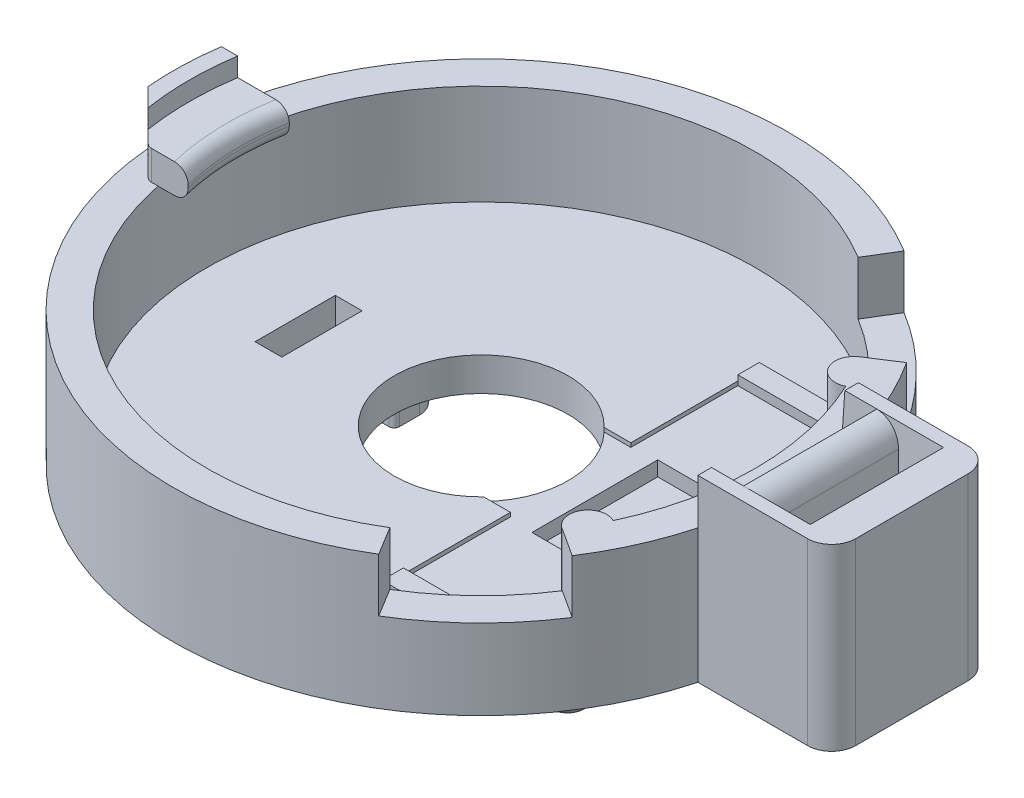
SolidWorks part; units mm, degrees
ref_plane "Спереди" through (0, 0, 0) normal (0, 0, 1) x (1, 0, 0)
ref_plane "Сверху" through (0, 0, 0) normal (0, 1, 0) x (1, 0, 0)
ref_plane "Справа" through (0, 0, 0) normal (1, 0, 0) x (0, 0, -1)
sketch "Sketch3" plane through (0, 0, 0) normal (0, 1, 0) x (1, 0, 0)
  circle A0 centre (0, 0) radius 11.5
  dimension "D1" = 23
extrude "Boss-Extrude2" add sketch "Sketch3" along normal blind 5
sketch "Sketch4" plane through (0, 5, 0) normal (0, 1, 0) x (1, 0, 0)
  circle A0 centre (0, 0) radius 10.25
  dimension "D1" = 20.5
extrude "Cut-Extrude2" cut sketch "Sketch4" against normal offset from surface (3.75 mm away) 1.25 up to face at (0, 0, 11.5)
sketch "Sketch5" plane through (0, 0, 0) normal (0, -1, 0) x (1, 0, 0)
  line L0 (11.1018, 0) -> (0, 0) construction
  line L1 (11.1018, 3) -> (16.1, 3)
  line L2 (11.1018, 3) -> (11.1018, -3)
  line L3 (11.1018, -3) -> (16.1, -3)
  line L4 (16.1, 3) -> (16.1, -3)
  line L5 (-11.5, 0) -> (0, 0) construction
  circle A0 centre (0, 0) radius 11.5 construction
  dimension "D1" = 6
  dimension "D2" = 27.6
extrude "Boss-Extrude3" add sketch "Sketch5" against normal blind 6.7
fillet "Fillet1" radius 0.9 2 edges at (16.1, 3.35, -3) (16.1, 3.35, 3)
sketch "Sketch6" plane through (0, 1.25, 0) normal (0, 1, 0) x (1, 0, 0)
  circle A0 centre (0, 0) radius 3.25
  dimension "D1" = 6.5
extrude "Cut-Extrude3" cut sketch "Sketch6" against normal through all
sketch "Sketch8" plane through (0, 5, 0) normal (0, 1, 0) x (1, 0, 0)
  line L0 (5.9896, 9.8171) -> (5.3385, 8.75)
  line L1 (9.6534, 6.25) -> (8.6041, 5.5707)
  line L2 (9.6534, -6.25) -> (8.6041, -5.5707)
  line L3 (5.9896, -9.8171) -> (5.3385, -8.75)
  line L4 (5.3385, 8.75) -> (0, 0) construction
  line L5 (0, 0) -> (8.6041, 5.5707) construction
  line L6 (0, 0) -> (5.3385, -8.75) construction
  line L7 (0, 0) -> (8.6041, -5.5707) construction
  line L8 (9.6534, 6.25) -> (9.6534, -6.25) construction
  line L9 (9.6534, 0) -> (0, 0) construction
  line L10 (5.9896, 9.8171) -> (5.9896, -9.8171) construction
  arc A0 (5.9896, 9.8171) -> (9.6534, 6.25) centre (0, 0) cw
  arc A1 (11.1018, 3) -> (11.1018, -3) centre (0, 0) ccw construction
  arc A2 (9.6534, -6.25) -> (5.9896, -9.8171) centre (0, 0) cw
  arc A3 (5.3385, 8.75) -> (8.6041, 5.5707) centre (-1.1445, -1.1755) cw
  circle A4 centre (0, 0) radius 10.25 construction
  arc A5 (8.6041, -5.5707) -> (5.3385, -8.75) centre (0, 0) cw
  dimension "D1" = 12.5
  dimension "D2" = 17.5
extrude "Cut-Extrude4" cut sketch "Sketch8" against normal blind 2
sketch "Sketch9" plane through (0, 0, 0) normal (0, -1, 0) x (1, 0, 0)
  line L0 (-7.8208, 4.4537) -> (-2.8242, 1.6083) construction
  line L1 (-1.4647, 3.9955) -> (-4.1836, -0.7789) construction
  line L2 (-7.8208, 4.4537) -> (0.0534, -8.9998) construction
  line L3 (0.0534, -8.9998) -> (7.7674, 4.5461) construction
  line L4 (7.7674, 4.5461) -> (-7.8208, 4.4537) construction
  circle A0 centre (7.7674, 4.5461) radius 0.75
  circle A1 centre (0.0534, -8.9998) radius 0.75
  circle A2 centre (-7.8208, 4.4537) radius 0.75
  circle A3 centre (0, 0) radius 9 construction
  circle A5 centre (0, 0) radius 3.25 construction
  dimension "D1" = 1.5
  dimension "D2" = 5.75
  dimension "D3" = 8.25
extrude "Boss-Extrude4" add sketch "Sketch9" along normal blind 1.5
fillet "Fillet2" radius 0.3 3 edges at (7.7674, -1.5, 3.7961) (-7.8208, -1.5, 3.7037) (0.0534, -1.5, -9.7498)
sketch "Sketch10" plane through (0, 0, 0) normal (0, -1, 0) x (1, 0, 0)
  line L0 (0, 0) -> (-11.247, 2.3989) construction
  line L1 (-11.486, -0.5665) -> (-10.2343, -0.5665)
  line L2 (-10.2553, 5.2037) -> (-8.8309, 5.2037)
  arc A0 (-11.486, -0.5665) -> (-10.2553, 5.2037) centre (0, 0) cw
  arc A1 (11.1018, 3) -> (11.1018, -3) centre (0, 0) ccw construction
  arc A2 (-10.2343, -0.5665) -> (-8.8309, 5.2037) centre (0, 0) cw
  arc A3 (5.3385, 8.75) -> (5.3385, -8.75) centre (0, 0) ccw construction
  circle A4 centre (-7.8208, 4.4537) radius 0.75 construction
  dimension "D1" = 5.9
extrude "Boss-Extrude5" add sketch "Sketch10" along normal up to surface (1.5 mm away) up to face at (-7.8208, -1.5, 4.0037)
sketch "Sketch11" plane through (0, 5, 0) normal (0, 1, 0) x (1, 0, 0)
  line L0 (0, 0) -> (-10.9, 0) construction
  line L1 (-11.3777, 1.6727) -> (-10.7709, 1.6727)
  line L2 (-10.7709, -1.6727) -> (-11.4577, -0.9859)
  line L3 (-10.9, -7.6089) -> (-10.9, 7.6089) construction
  arc A0 (-11.3777, 1.6727) -> (-11.4577, -0.9859) centre (0, 0) ccw
  arc A1 (5.9896, 9.8171) -> (5.9896, -9.8171) centre (0, 0) ccw construction
  arc A2 (-10.7709, -1.6727) -> (-10.7709, 1.6727) centre (0, 0) cw
  dimension "D2" = 0.6
  dimension "D1" = 45
  dimension "D3" = 3.4
extrude "Boss-Extrude7" add sketch "Sketch11" along normal blind 2
sketch "Sketch12" plane through (0, 1.25, 0) normal (0, 1, 0) x (1, 0, 0)
  line L0 (-5.95, 1.5) -> (-5.95, -1.5)
  line L1 (-5.95, -1.5) -> (-6.95, -1.5)
  line L2 (-6.95, -1.5) -> (-6.95, 1.5)
  line L3 (-6.95, 1.5) -> (-5.95, 1.5)
  line L4 (-5.95, 0) -> (-3.25, 0) construction
  line L5 (-3.25, 0) -> (0, 0) construction
  circle A0 centre (0, 0) radius 3.25 construction
  dimension "D1" = 2.7
  dimension "D2" = 1
  dimension "D3" = 3
extrude "Cut-Extrude5" cut sketch "Sketch12" against normal through all
sketch "Sketch13" plane through (0, 0, 0) normal (0, -1, 0) x (1, 0, 0)
  line L0 (-6.95, 1) -> (-6.95, 1.5)
  line L1 (-6.95, -1.5) -> (-6.95, 1.5) construction
  line L2 (-6.95, 1.5) -> (-5.95, 1.5)
  line L3 (-5.95, 1.5) -> (-5.95, -1.5)
  line L4 (-5.95, -1.5) -> (-6.95, -1.5)
  line L5 (-6.95, -1.5) -> (-6.95, -1)
  line L6 (-6.95, -1) -> (-7.75, -1)
  line L7 (-7.75, -1) -> (-7.75, -2.75)
  line L8 (-7.75, -2.75) -> (-4.25, -2.75)
  line L9 (-4.25, -2.75) -> (-4.25, -1)
  line L10 (-4.25, -1) -> (-5.15, -1)
  line L11 (-5.15, -1) -> (-5.15, 1)
  line L12 (-5.15, 1) -> (-4.25, 1)
  line L13 (-4.25, 1) -> (-4.25, 2.75)
  line L14 (-4.25, 2.75) -> (-7.75, 2.75)
  line L15 (-7.75, 2.75) -> (-7.75, 1)
  line L16 (-7.75, 1) -> (-6.95, 1)
  line L17 (-7.75, 1) -> (-7.75, -1) construction
  line L18 (-7.75, 0) -> (-3.25, 0) construction
  line L19 (-7.75, 0) -> (-6.95, 0) construction
  circle A0 centre (0, 0) radius 3.25 construction
  dimension "D1" = 3.5
  dimension "D2" = 0.8
  dimension "D3" = 4.5
  dimension "D4" = 5.5
  dimension "D5" = 2
extrude "Boss-Extrude8" add sketch "Sketch13" along normal up to surface (1.5 mm away) up to face at (-7.8208, -1.5, 4.0037)
fillet "Fillet3" radius 0.8 4 edges at (-4.25, -0.75, -2.75) (-7.75, -0.75, -2.75) (-4.25, -0.75, 2.75) (-7.75, -0.75, 2.75)
fillet "Fillet4" radius 0.2 4 edges at (-4.25, -0.75, -1) (-5.15, -0.75, -1) (-5.15, -0.75, 1) (-4.25, -0.75, 1)
sketch "Sketch14" plane through (0, 0, 0) normal (0, -1, 0) x (1, 0, 0)
  line L0 (14.3, 0.6) -> (14.3, -0.6)
  line L1 (14.3, -0.6) -> (14.1, -0.6)
  line L2 (14.1, -0.6) -> (14.1, -2)
  line L3 (14.1, -2) -> (13.6, -2)
  line L4 (13.6, -2) -> (13.6, 2)
  line L5 (13.6, 2) -> (14.1, 2)
  line L6 (14.1, 2) -> (14.1, 0.6)
  line L7 (14.1, 0.6) -> (14.3, 0.6)
  line L8 (16.1, -2.1) -> (16.1, 2.1) construction
  line L9 (13.6, 0) -> (14.3, 0) construction
  line L10 (14.3, 0) -> (16.1, 0) construction
  dimension "D1" = 0.5
  dimension "D2" = 1.8
  dimension "D3" = 2
  dimension "D4" = 1.2
  dimension "D5" = 4
extrude "Cut-Extrude6" cut sketch "Sketch14" against normal through all draft 4.2 draft outward yes
fillet "Fillet5" radius 0.9 1 edges at (13.108, 6.7, 0)
sketch "Sketch16" plane through (0, 0, 0) normal (0, 0, 1) x (1, 0, 0)
  line L0 (12.3, 6.7) -> (11.1018, 5.5018)
  line L1 (11.1018, 5.5018) -> (10.9018, 5.5018)
  line L2 (10.9018, 5.5018) -> (10.9018, 6.7)
  line L3 (10.9018, 6.7) -> (12.3, 6.7)
  line L4 (15.2, 6.7) -> (11.1018, 6.7) construction
  line L5 (16.1, 6.7) -> (16.1, 0) construction
  line L6 (11.1018, 6.7) -> (11.1018, 5) construction
  dimension "D1" = 45
  dimension "D2" = 3.8
  dimension "D3" = 0.2
extrude "Cut-Extrude7" cut sketch "Sketch16" against normal up to surface and the other way up to surface up to face at (13.5794, 3.8884, -2.2855) other way up to face at (13.5794, 3.8884, 2.2855)
sketch "Sketch17" plane through (0, 6.7, 0) normal (0, 1, 0) x (1, 0, 0)
  line L0 (11.1018, 2.492) -> (14.592, 2.492) construction
  line L1 (13.392, 2.492) -> (14.792, 2.492)
  line L2 (13.392, 2.492) -> (13.392, -2.492)
  line L3 (13.392, -2.492) -> (14.792, -2.492)
  line L4 (14.792, 2.492) -> (14.792, -2.492)
  line L5 (14.592, -2.492) -> (11.1018, -2.492) construction
  line L7 (14.592, 2.492) -> (14.592, 1.092) construction
  line L9 (14.792, 1.092) -> (14.792, -1.092) construction
  dimension "D2" = 1.2
extrude "Cut-Extrude8" cut sketch "Sketch17" against normal blind 0.4 draft 4.2
sketch "Sketch18" plane through (0, 1.25, 0) normal (0, 1, 0) x (1, 0, 0)
  line L0 (4.25, 0) -> (0, 0) construction
  line L1 (4.25, 2.35) -> (6.25, 2.35)
  line L2 (4.25, 2.35) -> (4.25, -2.35)
  line L3 (4.25, -2.35) -> (6.25, -2.35)
  line L4 (6.25, 2.35) -> (6.25, -2.35)
  line L5 (3.25, 0) -> (4.25, 0) construction
  circle A0 centre (0, 0) radius 3.25 construction
  dimension "D1" = 4.7
  dimension "D2" = 2
  dimension "D3" = 1
extrude "Cut-Extrude9" cut sketch "Sketch18" against normal blind 0.7
sketch "Sketch19" plane through (0, 1.25, 0) normal (0, 1, 0) x (1, 0, 0)
  line L0 (2.3452, 2.25) -> (3.3452, 2.25)
  line L1 (3.3452, 2.25) -> (3.3452, 6.25)
  line L2 (3.3452, 6.25) -> (8.124, 6.25)
  line L3 (2.3452, -2.25) -> (3.3452, -2.25)
  line L4 (3.3452, -2.25) -> (3.3452, -6.25)
  line L5 (3.3452, -6.25) -> (8.124, -6.25)
  line L6 (3.25, 0) -> (0, 0) construction
  circle A0 centre (0, 0) radius 10.25 construction
  arc A1 (8.124, 6.25) -> (8.124, -6.25) centre (0, 0) cw
  circle A2 centre (0, 0) radius 3.25 construction
  arc A3 (2.3452, 2.25) -> (2.3452, -2.25) centre (0, 0) cw
  dimension "D1" = 4.5
  dimension "D2" = 12.5
  dimension "D3" = 1
extrude "Cut-Extrude10" cut sketch "Sketch19" against normal blind 0.15
sketch "Sketch20" plane through (0, 1.25, 0) normal (0, 1, 0) x (1, 0, 0)
  line L1 (3.3452, 6.25) -> (8.124, 6.25)
  line L2 (3.3452, 6.25) -> (3.3452, 7.05)
  line L3 (3.3452, 7.05) -> (8.124, 7.05)
  line L4 (8.124, 6.25) -> (8.124, 7.05)
  line L5 (3.3452, -6.25) -> (8.124, -6.25)
  line L6 (3.3452, -6.25) -> (3.3452, -7.05)
  line L7 (3.3452, -7.05) -> (8.124, -7.05)
  line L8 (8.124, -6.25) -> (8.124, -7.05)
  dimension "D1" = 0.8
extrude "Boss-Extrude9" add sketch "Sketch20" along normal blind 0.2
sketch "Sketch21" plane through (0, 1.1, 0) normal (0, 1, 0) x (1, 0, 0)
  line L0 (8.9642, 4.9704) -> (8.9642, -4.9704) construction
  line L1 (8.9642, 0) -> (0, 0) construction
  line L2 (8.352, -4.631) -> (8.9642, -4.9704) construction
  arc A0 (8.6041, 5.5707) -> (9.2826, 4.347) centre (8.9642, 4.9704) ccw
  arc A1 (8.124, -6.25) -> (8.124, 6.25) centre (0, 0) ccw construction
  arc A2 (9.2826, -4.347) -> (8.6041, -5.5707) centre (8.9642, -4.9704) ccw
  arc A3 (8.9642, -4.9704) -> (8.9642, 4.9704) centre (0, 0) ccw construction
  arc A4 (8.6041, -5.5707) -> (8.6041, 5.5707) centre (0, 0) ccw construction
  arc A5 (5.3385, -8.75) -> (8.6041, -5.5707) centre (0, 0) ccw construction
  arc A6 (8.6041, 5.5707) -> (9.2826, 4.347) centre (0, 0) cw
  arc A7 (9.2826, -4.347) -> (8.6041, -5.5707) centre (0, 0) cw
  dimension "D1" = 0.7
extrude "Boss-Extrude10" add sketch "Sketch21" along normal up to surface (3.9 mm away) up to face at (10.1029, 5, 0)
sketch "Sketch23" plane through (0, 1.1, 0) normal (0, 1, 0) x (1, 0, 0)
  line L0 (6.25, -2.35) -> (6.25, 2.35) construction
  line L1 (10.1672, 2.35) -> (6.25, 2.35)
  line L2 (10.1672, 2.35) -> (10.1672, 1.3)
  line L3 (10.1672, 1.3) -> (6.25, 1.3)
  line L4 (6.25, 2.35) -> (6.25, 1.3)
  line L5 (10.1672, -1.3) -> (6.25, -1.3)
  line L6 (10.1672, -1.3) -> (10.1672, -2.35)
  line L7 (10.1672, -2.35) -> (6.25, -2.35)
  line L8 (6.25, -1.3) -> (6.25, -2.35)
  line L9 (6.25, 2.35) -> (4.25, 2.35) construction
  line L10 (4.25, -2.35) -> (6.25, -2.35) construction
  arc A0 (9.2826, -4.347) -> (9.2826, 4.347) centre (0, 0) ccw construction
  dimension "D1" = 2.6
extrude "Boss-Extrude13" add sketch "Sketch23" along normal up to surface (0.15 mm away) up to face at (-6.45, 1.25, 0)
fillet "Fillet6" radius 0.2 1 edges at (6.25, 1.25, -1.825)
sketch "Sketch24" plane through (0, 5, 0) normal (0, 1, 0) x (1, 0, 0)
  line L0 (-10.7709, 1.6727) -> (-8.8442, 1.6727)
  line L1 (-10.7709, -1.6727) -> (-10.2163, -2.2273)
  line L2 (-11.4577, -0.9859) -> (-10.7709, -1.6727) construction
  line L3 (-10.2163, -2.2273) -> (-8.721, -2.2273)
  line L4 (-8.9965, -0.284) -> (-11.4965, -0.284) construction
  arc A0 (-8.721, -2.2273) -> (-8.8442, 1.6727) centre (0, 0) cw
  arc A1 (-10.7709, 1.6727) -> (-10.7709, -1.6727) centre (0, 0) ccw
  arc A2 (-10.7709, 1.6727) -> (-10.7709, -1.6727) centre (0, 0) ccw construction
  arc A3 (-11.3777, 1.6727) -> (-11.4577, -0.9859) centre (0, 0) ccw construction
  dimension "D1" = 3.9
  dimension "D2" = 2.5
extrude "Boss-Extrude14" add sketch "Sketch24" along normal offset from surface (1.1 mm away) 0.7 from offset 0.2 up to face at (-11.1458, 7, -0.1723)
fillet "Fillet7" radius 0.5 2 edges at (-8.9965, 6.3, 0.284) (-8.9965, 5.2, 0.284)
fillet "Fillet8" radius 0.3 1 edges at (-10.2163, 5.75, 2.2273)
equation "\"D2@Sketch9\"=6.5-\"D1@Sketch9\"/2"
equation "\"D3@Sketch9\"=9-\"D1@Sketch9\"/2"
